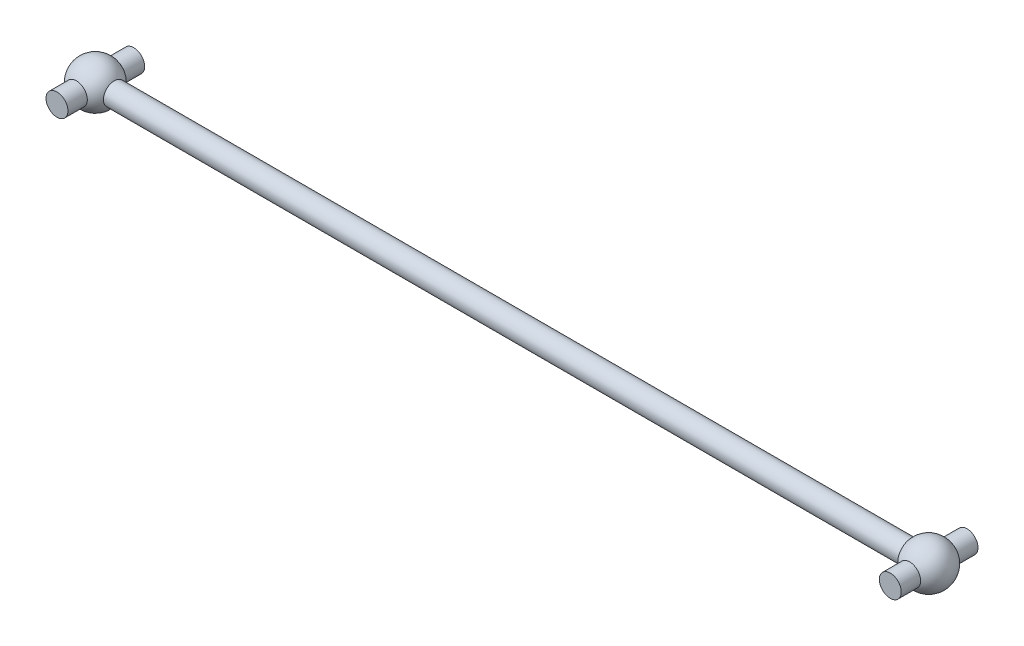
SolidWorks part; units mm, degrees
ref_plane "Front" through (0, 0, 0) normal (0, 0, 1) x (1, 0, 0)
ref_plane "Top" through (0, 0, 0) normal (0, 1, 0) x (1, 0, 0)
ref_plane "Right" through (0, 0, 0) normal (1, 0, 0) x (0, 0, -1)
sketch "Sketch1" plane through (0, 0, 0) normal (0, 0, 1) x (1, 0, 0)
  line L0 (0, 0) -> (120.65, 0) construction
  line L1 (0, 1.5875) -> (120.65, 1.5875) construction
  line L2 (2.7496, 1.5875) -> (117.9004, 1.5875)
  line L3 (123.825, 0) -> (-3.175, 0)
  circle A0 centre (0, 0) radius 3.175
  circle A1 centre (120.65, 0) radius 3.175
  circle A2 centre (0, 0) radius 1.5875
  circle A3 centre (120.65, 0) radius 1.5875
  dimension "D1" = 6.35
  dimension "D5" = 3.175
  dimension "D2" = 120.65
  dimension "D4" = 1.5875
revolve "Revolve1" add sketch "Sketch1" angle 360 about L3 region at (60.325, 0.7947, 0) region at (2.9982, 0.8034, 0) region at (121.4534, 2.9982, 0) region at (0, 0.6738, 0) region at (120.65, 0.6738, 0)
extrude "Boss-Extrude1" add sketch "Sketch1<3>" along normal mid plane 11.1125 contours L3 A3 | L3 A3 | L3 A2 | L3 A2 region at (0, -0.6738, 0) region at (0, 0.6738, 0) region at (120.65, -0.6738, 0) region at (120.65, 0.6738, 0)
sketch "Sketch1<3>" plane through (0, 0, 0) normal (0, 0, 1) x (1, 0, 0) same geometry as "Sketch1"
ref_axis "Axis1" through (2.7496, 0, 0) along (1, 0, 0)
ref_axis "Axis2" through (120.65, 0, -2.7496) along (0, 0, -1)
